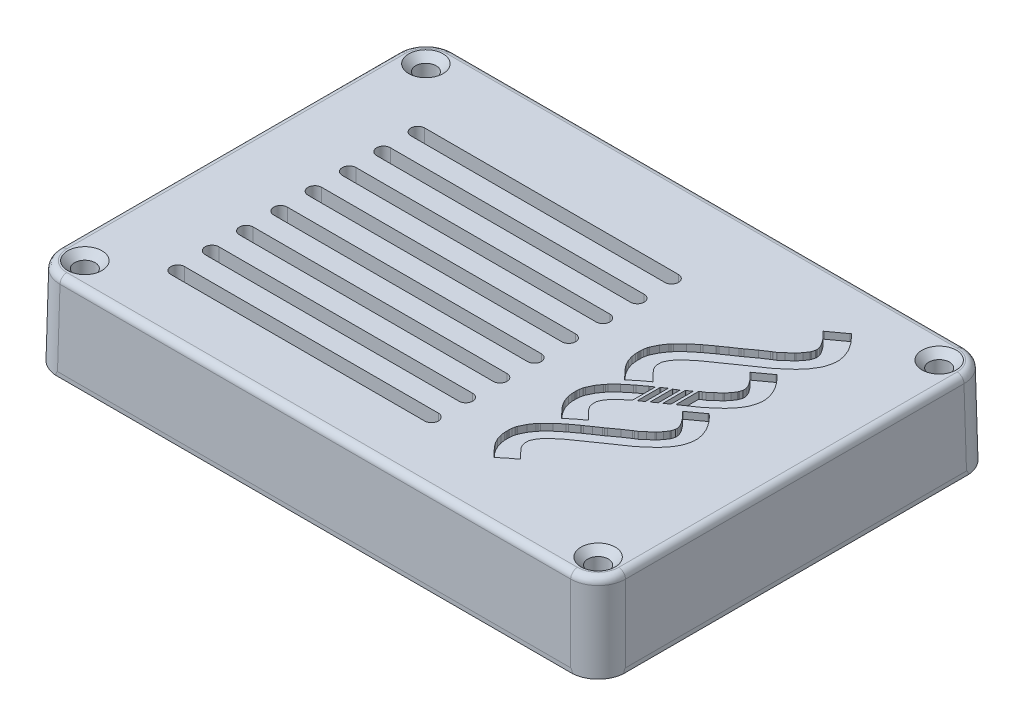
SolidWorks part; units mm, degrees
material "ABS PC"
ref_plane "Front Plane" through (0, 0, 0) normal (0, 0, 1) x (1, 0, 0)
ref_plane "Top Plane" through (0, 0, 0) normal (0, 1, 0) x (1, 0, 0)
ref_plane "Right Plane" through (0, 0, 0) normal (1, 0, 0) x (0, 0, -1)
sketch "Sketch1" plane through (0, 0, 0) normal (0, 1, 0) x (1, 0, 0)
  line L1 (-108.7297, 31.1354) -> (-25.9297, 31.1354)
  line L2 (-108.7297, 31.1354) -> (-108.7297, -26.5646)
  line L3 (-108.7297, -26.5646) -> (-25.9297, -26.5646)
  line L4 (-25.9297, 31.1354) -> (-25.9297, -26.5646)
  line L5 (-108.7297, 31.1354) -> (-25.9297, -26.5646) construction
  line L6 (-108.7297, -26.5646) -> (-25.9297, 31.1354) construction
  point P0 (-67.3297, 2.2854)
extrude "Boss-Extrude1" add sketch "Sketch1" along normal blind 12.6
chamfer "Chamfer1" distance 12 distance2 0.2 4 edges at (-25.9297, 12.6, -2.2854) (-67.3297, 12.6, -31.1354) (-108.7297, 12.6, -2.2854) (-67.3297, 12.6, 26.5646) first distance on face at (-25.9297, 6.3, -2.2854) first distance on face at (-67.3297, 6.3, -31.1354) first distance on face at (-108.7297, 6.3, -2.2854) first distance on face at (-67.3297, 6.3, 26.5646)
fillet "Fillet1" radius 4 4 edges at (-108.6297, 6.6, -31.0354) (-26.0297, 6.6, -31.0354) (-26.0297, 6.6, 26.4646) (-108.6297, 6.6, 26.4646)
sketch "Sketch2" plane through (0, 0, 0) normal (0, -1, 0) x (1, 0, 0)
  circle A0 centre (-104.7391, 22.5741) radius 1.5
  circle A1 centre (-29.9202, 22.5741) radius 1.5
  circle A2 centre (-104.7391, -27.1448) radius 1.5
  circle A3 centre (-29.9202, -27.1448) radius 1.5
extrude "Cut-Extrude1" cut sketch "Sketch2" against normal blind 12.6
fillet "Fillet2" radius 1 8 edges at (-107.3583, 12.6, -29.764) (-67.3297, 12.6, -30.9354) (-27.301, 12.6, -29.764) (-26.1297, 12.6, -2.2854) (-27.301, 12.6, 25.1933) (-67.3297, 12.6, 26.3646) (-107.3583, 12.6, 25.1933) (-108.5297, 12.6, -2.2854)
chamfer "Chamfer2" distance 1 angle 45 4 edges at (-104.7391, 12.6, 21.0741) (-29.9202, 12.6, 21.0741) (-29.9202, 12.6, -28.6448) (-104.7391, 12.6, -28.6448)
sketch "Sketch3" plane through (0, 0, 0) normal (0, -1, 0) x (1, 0, 0)
  line L0 (-105.0229, 26.5646) -> (-29.6364, 26.5646) construction
  line L1 (-99.7651, 22.0646) -> (-34.8942, 22.0646)
  line L2 (-104.2297, 17.6001) -> (-104.2297, -22.1708)
  line L3 (-99.7651, -26.6354) -> (-34.8942, -26.6354)
  line L4 (-30.4297, 17.6001) -> (-30.4297, -22.1708)
  line L5 (-100.7693, 23.0646) -> (-33.89, 23.0646)
  line L6 (-29.4297, 18.6043) -> (-29.4297, -23.175)
  line L7 (-108.7297, -27.4286) -> (-108.7297, 22.8579) construction
  line L8 (-25.9297, 22.8579) -> (-25.9297, -27.4286) construction
  line L9 (-29.6364, -31.1354) -> (-105.0229, -31.1354) construction
  line L10 (-100.7693, -27.6354) -> (-33.89, -27.6354)
  line L11 (-105.2297, 18.6043) -> (-105.2297, -23.175)
  arc A0 (-104.2297, 17.6001) -> (-99.7651, 22.0646) centre (-104.7391, 22.5741) ccw
  arc A1 (-34.8942, 22.0646) -> (-30.4297, 17.6001) centre (-29.9202, 22.5741) ccw
  arc A2 (-30.4297, -22.1708) -> (-34.8942, -26.6354) centre (-29.9202, -27.1448) ccw
  arc A3 (-99.7651, -26.6354) -> (-104.2297, -22.1708) centre (-104.7391, -27.1448) ccw
  arc A4 (-33.89, 23.0646) -> (-29.4297, 18.6043) centre (-29.9202, 22.5741) ccw
  arc A5 (-29.4297, -23.175) -> (-33.89, -27.6354) centre (-29.9202, -27.1448) ccw
  arc A6 (-100.7693, -27.6354) -> (-105.2297, -23.175) centre (-104.7391, -27.1448) ccw
  arc A7 (-105.2297, 18.6043) -> (-100.7693, 23.0646) centre (-104.7391, 22.5741) ccw
  point P0 (-67.3297, -2.2854)
  dimension "D5" = 1
  dimension "D1" = 4.5
  dimension "D2" = 4.5
  dimension "D3" = 4.5
  dimension "D4" = 4.5
extrude "Cut-Extrude2" cut sketch "Sketch3" against normal blind 10.4 contours A0 L1 A1 L4 A2 L3 A3 L2
extrude "Cut-Extrude-Thin1" cut sketch "Sketch3<4>" against normal blind 1 thin contours L11 A6 L10 A5 L6 A4 L5 A7 thin type one direction wall 1
sketch "Sketch3<4>" plane through (0, 0, 0) normal (0, -1, 0) x (1, 0, 0) same geometry as "Sketch3"
sketch "Sketch4" plane through (0, 12.6, 0) normal (0, 1, 0) x (1, 0, 0)
  line L0 (-96.7297, 18.9519) -> (-59.7297, 18.9519)
  line L1 (-96.7297, 16.9519) -> (-59.7297, 16.9519)
  line L2 (-30.1127, 29.9519) -> (-104.5466, 29.9519) construction
  line L3 (-96.7297, 18.9519) -> (-96.7297, 16.9519) construction
  line L4 (-59.7297, 18.9519) -> (-59.7297, 16.9519) construction
  line L5 (-96.7297, 13.9519) -> (-59.7297, 13.9519)
  line L6 (-96.7297, 11.9519) -> (-59.7297, 11.9519)
  line L7 (-96.7297, 13.9519) -> (-96.7297, 11.9519) construction
  line L8 (-59.7297, 13.9519) -> (-59.7297, 11.9519) construction
  line L9 (-96.7297, 8.9519) -> (-59.7297, 8.9519)
  line L10 (-96.7297, 6.9519) -> (-59.7297, 6.9519)
  line L11 (-96.7297, 8.9519) -> (-96.7297, 6.9519) construction
  line L12 (-59.7297, 8.9519) -> (-59.7297, 6.9519) construction
  line L13 (-96.7297, 3.9519) -> (-59.7297, 3.9519)
  line L14 (-96.7297, 1.9519) -> (-59.7297, 1.9519)
  line L15 (-96.7297, 3.9519) -> (-96.7297, 1.9519) construction
  line L16 (-59.7297, 3.9519) -> (-59.7297, 1.9519) construction
  line L17 (-96.7297, -1.0481) -> (-59.7297, -1.0481)
  line L18 (-96.7297, -3.0481) -> (-59.7297, -3.0481)
  line L19 (-96.7297, -1.0481) -> (-96.7297, -3.0481) construction
  line L20 (-59.7297, -1.0481) -> (-59.7297, -3.0481) construction
  line L21 (-96.7297, -6.0481) -> (-59.7297, -6.0481)
  line L22 (-96.7297, -8.0481) -> (-59.7297, -8.0481)
  line L23 (-96.7297, -6.0481) -> (-96.7297, -8.0481) construction
  line L24 (-59.7297, -6.0481) -> (-59.7297, -8.0481) construction
  line L25 (-96.7297, -11.0481) -> (-59.7297, -11.0481)
  line L26 (-96.7297, -13.0481) -> (-59.7297, -13.0481)
  line L27 (-96.7297, -11.0481) -> (-96.7297, -13.0481) construction
  line L28 (-59.7297, -11.0481) -> (-59.7297, -13.0481) construction
  line L29 (-96.7297, -16.0481) -> (-59.7297, -16.0481)
  line L30 (-96.7297, -18.0481) -> (-59.7297, -18.0481)
  line L31 (-96.7297, -16.0481) -> (-96.7297, -18.0481) construction
  line L32 (-59.7297, -16.0481) -> (-59.7297, -18.0481) construction
  line L33 (-108.7297, -22.5652) -> (-108.7297, 27.1359) construction
  arc A0 (-96.7297, 18.9519) -> (-96.7297, 16.9519) centre (-96.7297, 17.9519) ccw
  arc A1 (-59.7297, 16.9519) -> (-59.7297, 18.9519) centre (-59.7297, 17.9519) ccw
  arc A2 (-96.7297, 13.9519) -> (-96.7297, 11.9519) centre (-96.7297, 12.9519) ccw
  arc A3 (-59.7297, 11.9519) -> (-59.7297, 13.9519) centre (-59.7297, 12.9519) ccw
  arc A4 (-96.7297, 8.9519) -> (-96.7297, 6.9519) centre (-96.7297, 7.9519) ccw
  arc A5 (-59.7297, 6.9519) -> (-59.7297, 8.9519) centre (-59.7297, 7.9519) ccw
  arc A6 (-96.7297, 3.9519) -> (-96.7297, 1.9519) centre (-96.7297, 2.9519) ccw
  arc A7 (-59.7297, 1.9519) -> (-59.7297, 3.9519) centre (-59.7297, 2.9519) ccw
  arc A8 (-96.7297, -1.0481) -> (-96.7297, -3.0481) centre (-96.7297, -2.0481) ccw
  arc A9 (-59.7297, -3.0481) -> (-59.7297, -1.0481) centre (-59.7297, -2.0481) ccw
  arc A10 (-96.7297, -6.0481) -> (-96.7297, -8.0481) centre (-96.7297, -7.0481) ccw
  arc A11 (-59.7297, -8.0481) -> (-59.7297, -6.0481) centre (-59.7297, -7.0481) ccw
  arc A12 (-96.7297, -11.0481) -> (-96.7297, -13.0481) centre (-96.7297, -12.0481) ccw
  arc A13 (-59.7297, -13.0481) -> (-59.7297, -11.0481) centre (-59.7297, -12.0481) ccw
  arc A14 (-96.7297, -16.0481) -> (-96.7297, -18.0481) centre (-96.7297, -17.0481) ccw
  arc A15 (-59.7297, -18.0481) -> (-59.7297, -16.0481) centre (-59.7297, -17.0481) ccw
  dimension "D4" = 37
  dimension "D5" = 12
  dimension "D1" = 2
  dimension "D2" = 11
  dimension "D3" = 8
extrude "Cut-Extrude3" cut sketch "Sketch4" against normal blind 10.4
sketch "Sketch5" plane through (0, 12.6, -12.6) normal (0, -1, 0) x (1, 0, 0)
  line L156 (-52.4746, 25.5513) -> (-52.4746, 25.6597)
  line L157 (-52.4528, 25.2263) -> (-52.4746, 25.5513)
  line L158 (-52.372, 24.8216) -> (-52.4528, 25.2263)
  line L159 (-52.3429, 24.7362) -> (-52.372, 24.8216)
  line L160 (-52.2772, 24.543) -> (-52.3429, 24.7362)
  line L168 (-51.8523, 23.6409) -> (-52.2772, 24.543)
  line L169 (-51.3033, 22.8336) -> (-51.8523, 23.6409)
  line L170 (-51.1752, 22.6873) -> (-51.3033, 22.8336)
  line L171 (-51.01, 22.4982) -> (-51.1752, 22.6873)
  line L172 (-50.1017, 21.5946) -> (-51.01, 22.4982)
  line L173 (-49.0694, 20.7342) -> (-50.1017, 21.5946)
  line L174 (-48.8419, 20.5665) -> (-49.0694, 20.7342)
  line L175 (-47.8226, 19.8143) -> (-48.8419, 20.5665)
  line L176 (-47.7362, 19.7509) -> (-47.8226, 19.8143)
  line L177 (-47.7263, 19.7628) -> (-47.7362, 19.7509)
  line L178 (-47.5783, 19.6555) -> (-47.7263, 19.7628)
  line L179 (-46.7856, 19.0893) -> (-47.5783, 19.6555)
  line L180 (-45.9424, 18.5191) -> (-46.7856, 19.0893)
  line L181 (-45.7689, 18.4092) -> (-45.9424, 18.5191)
  line L182 (-45.5184, 18.218) -> (-45.7689, 18.4092)
  line L183 (-44.3725, 17.381) -> (-45.5184, 18.218)
  line L184 (-43.3778, 16.7096) -> (-44.3725, 17.381)
  line L185 (-43.2028, 16.6008) -> (-43.3778, 16.7096)
  line L186 (-43.1716, 16.5815) -> (-43.2028, 16.6008)
  line L187 (-42.8658, 16.3978) -> (-43.1716, 16.5815)
  line L188 (-42.8361, 16.3806) -> (-42.8658, 16.3978)
  line L189 (-42.2205, 15.8363) -> (-42.8361, 16.3806)
  line L190 (-41.5361, 15.2311) -> (-42.2205, 15.8363)
  line L191 (-41.4367, 15.1238) -> (-41.5361, 15.2311)
  line L192 (-40.9741, 14.591) -> (-41.4367, 15.1238)
  line L193 (-40.6043, 14.0279) -> (-40.9741, 14.591)
  line L194 (-40.5512, 13.9055) -> (-40.6043, 14.0279)
  line L195 (-40.5257, 13.8462) -> (-40.5512, 13.9055)
  line L196 (-40.3975, 13.406) -> (-40.5257, 13.8462)
  line L279 (-40.3975, 13.2394) -> (-40.3975, 13.406)
  line L280 (-40.3975, 13.141) -> (-40.3975, 13.2394)
  line L281 (-40.4564, 12.8456) -> (-40.3975, 13.141)
  line L282 (-40.596, 12.503) -> (-40.4564, 12.8456)
  line L283 (-40.6366, 12.43) -> (-40.596, 12.503)
  line L284 (-40.721, 12.2811) -> (-40.6366, 12.43)
  line L285 (-41.234, 11.5743) -> (-40.721, 12.2811)
  line L286 (-41.9054, 10.8758) -> (-41.234, 11.5743)
  line L287 (-42.0689, 10.7311) -> (-41.9054, 10.8758)
  line L288 (-42.1752, 10.6367) -> (-42.0689, 10.7311)
  line L289 (-42.0606, 10.5534) -> (-42.1752, 10.6367)
  line L290 (-39.9939, 9.0462) -> (-42.0606, 10.5534)
  line L291 (-39.9189, 8.9915) -> (-39.9939, 9.0462)
  line L292 (-39.8496, 9.0539) -> (-39.9189, 8.9915)
  line L293 (-39.7028, 9.1878) -> (-39.8496, 9.0539)
  line L294 (-39.2809, 9.6096) -> (-39.7028, 9.1878)
  line L295 (-38.8366, 10.1257) -> (-39.2809, 9.6096)
  line L296 (-38.4741, 10.6367) -> (-38.8366, 10.1257)
  line L297 (-38.2278, 11.0389) -> (-38.4741, 10.6367)
  line L298 (-38.1507, 11.1754) -> (-38.2278, 11.0389)
  line L299 (-38.0559, 11.3435) -> (-38.1507, 11.1754)
  line L300 (-37.7231, 12.1982) -> (-38.0559, 11.3435)
  line L301 (-37.5793, 12.9779) -> (-37.7231, 12.1982)
  line L302 (-37.5793, 13.2377) -> (-37.5793, 12.9779)
  line L303 (-37.5793, 13.4478) -> (-37.5793, 13.2377)
  line L304 (-37.671, 14.0763) -> (-37.5793, 13.4478)
  line L305 (-37.8835, 14.7774) -> (-37.671, 14.0763)
  line L306 (-37.9439, 14.917) -> (-37.8835, 14.7774)
  line L307 (-38.0148, 15.0795) -> (-37.9439, 14.917)
  line L308 (-38.2715, 15.5478) -> (-38.0148, 15.0795)
  line L309 (-38.6486, 16.0982) -> (-38.2715, 15.5478)
  line L310 (-39.0512, 16.5857) -> (-38.6486, 16.0982)
  line L311 (-39.3522, 16.9185) -> (-39.0512, 16.5857)
  line L312 (-39.4533, 17.0279) -> (-39.3522, 16.9185)
  line L313 (-39.458, 17.0326) -> (-39.4533, 17.0279)
  line L314 (-39.5564, 17.1295) -> (-39.458, 17.0326)
  line L315 (-39.5606, 17.1336) -> (-39.5564, 17.1295)
  line L316 (-39.9825, 17.5066) -> (-39.5606, 17.1336)
  line L317 (-41.1377, 18.5144) -> (-39.9825, 17.5066)
  line L318 (-41.1423, 18.5185) -> (-41.1377, 18.5144)
  line L319 (-41.1476, 18.5227) -> (-41.1423, 18.5185)
  line L320 (-41.9815, 19.0972) -> (-41.1476, 18.5227)
  line L321 (-42.0721, 19.1602) -> (-41.9815, 19.0972)
  line L322 (-44.0949, 20.555) -> (-42.0721, 19.1602)
  line L323 (-47.1137, 22.6722) -> (-44.0949, 20.555)
  line L324 (-47.3001, 22.8097) -> (-47.1137, 22.6722)
  line L529 (-48.1398, 23.5086) -> (-47.3001, 22.8097)
  line L530 (-48.8715, 24.2347) -> (-48.1398, 23.5086)
  line L531 (-49.0034, 24.3857) -> (-48.8715, 24.2347)
  line L532 (-49.0731, 24.4654) -> (-49.0034, 24.3857)
  line L533 (-49.3752, 24.9112) -> (-49.0731, 24.4654)
  line L534 (-49.6148, 25.419) -> (-49.3752, 24.9112)
  line L535 (-49.6528, 25.5289) -> (-49.6148, 25.419)
  line L536 (-49.6533, 25.5336) -> (-49.6528, 25.5289)
  line L537 (-49.6569, 25.6274) -> (-49.6533, 25.5336)
  line L538 (-49.6569, 25.6597) -> (-49.6569, 25.6274)
  line L539 (-49.6569, 25.6904) -> (-49.6569, 25.6597)
  line L540 (-49.6559, 25.7821) -> (-49.6569, 25.6904)
  line L541 (-49.6553, 25.792) -> (-49.6559, 25.7821)
  line L542 (-49.6553, 25.8034) -> (-49.6553, 25.792)
  line L543 (-49.6548, 25.8201) -> (-49.6553, 25.8034)
  line L544 (-49.6548, 25.8336) -> (-49.6548, 25.8201)
  line L545 (-49.6533, 25.9393) -> (-49.6548, 25.8336)
  line L546 (-49.6533, 25.9789) -> (-49.6533, 25.9393)
  line L547 (-49.6533, 25.993) -> (-49.6533, 25.9789)
  line L548 (-49.6539, 26.0336) -> (-49.6533, 25.993)
  line L549 (-49.6539, 26.0378) -> (-49.6539, 26.0336)
  line L550 (-49.6539, 26.0524) -> (-49.6539, 26.0378)
  line L551 (-49.6539, 26.1961) -> (-49.6539, 26.0524)
  line L552 (-49.5263, 26.6274) -> (-49.6539, 26.1961)
  line L553 (-49.31, 26.9946) -> (-49.5263, 26.6274)
  line L554 (-49.2654, 27.0492) -> (-49.31, 26.9946)
  line L555 (-49.2189, 27.1071) -> (-49.2654, 27.0492)
  line L556 (-49.072, 27.2753) -> (-49.2189, 27.1071)
  line L557 (-48.7933, 27.5774) -> (-49.072, 27.2753)
  line L558 (-48.4351, 27.9508) -> (-48.7933, 27.5774)
  line L559 (-48.109, 28.2815) -> (-48.4351, 27.9508)
  line L560 (-47.9996, 28.3909) -> (-48.109, 28.2815)
  line L561 (-47.9064, 28.4847) -> (-47.9996, 28.3909)
  line L562 (-48.0127, 28.5628) -> (-47.9064, 28.4847)
  line L563 (-48.7559, 29.1112) -> (-48.0127, 28.5628)
  line L564 (-48.869, 29.1946) -> (-48.7559, 29.1112)
  line L565 (-49.8991, 30.0352) -> (-48.869, 29.1946)
  line L566 (-49.9944, 30.1216) -> (-49.8991, 30.0352)
  line L567 (-50.0752, 30.1951) -> (-49.9944, 30.1216)
  line L568 (-50.1517, 30.1175) -> (-50.0752, 30.1951)
  line L569 (-50.2653, 30.0034) -> (-50.1517, 30.1175)
  line L570 (-50.6033, 29.6581) -> (-50.2653, 30.0034)
  line L571 (-50.981, 29.2612) -> (-50.6033, 29.6581)
  line L572 (-51.2829, 28.9295) -> (-50.981, 29.2612)
  line L573 (-51.4543, 28.731) -> (-51.2829, 28.9295)
  line L574 (-51.5085, 28.6628) -> (-51.4543, 28.731)
  line L575 (-51.599, 28.5503) -> (-51.5085, 28.6628)
  line L576 (-51.8444, 28.1893) -> (-51.599, 28.5503)
  line L577 (-52.1548, 27.5951) -> (-51.8444, 28.1893)
  line L578 (-52.383, 26.8878) -> (-52.1548, 27.5951)
  line L579 (-52.4715, 26.2795) -> (-52.383, 26.8878)
  line L580 (-52.4715, 26.0763) -> (-52.4715, 26.2795)
  line L581 (-52.4715, 26.0623) -> (-52.4715, 26.0763)
  line L582 (-52.4715, 26.0185) -> (-52.4715, 26.0623)
  line L583 (-52.4709, 26.0133) -> (-52.4715, 26.0185)
  line L584 (-52.4709, 25.9795) -> (-52.4709, 26.0133)
  line L585 (-52.4709, 25.9529) -> (-52.4709, 25.9795)
  line L586 (-52.472, 25.8727) -> (-52.4709, 25.9529)
  line L587 (-52.472, 25.8628) -> (-52.472, 25.8727)
  line L588 (-52.4725, 25.8435) -> (-52.472, 25.8628)
  line L589 (-52.4731, 25.8289) -> (-52.4725, 25.8435)
  line L590 (-52.4746, 25.706) -> (-52.4731, 25.8289)
  line L591 (-52.4746, 25.6597) -> (-52.4746, 25.706)
  line L592 (-39.9189, -0.8716) -> (-39.9939, -0.8169)
  line L593 (-39.8502, -0.8091) -> (-39.9189, -0.8716)
  line L594 (-39.7033, -0.6752) -> (-39.8502, -0.8091)
  line L595 (-39.2809, -0.2533) -> (-39.7033, -0.6752)
  line L596 (-38.8366, 0.2629) -> (-39.2809, -0.2533)
  line L597 (-38.4741, 0.7738) -> (-38.8366, 0.2629)
  line L598 (-38.2278, 1.1757) -> (-38.4741, 0.7738)
  line L599 (-38.1507, 1.3122) -> (-38.2278, 1.1757)
  line L600 (-38.0559, 1.4805) -> (-38.1507, 1.3122)
  line L601 (-37.7231, 2.3352) -> (-38.0559, 1.4805)
  line L602 (-37.5793, 3.1153) -> (-37.7231, 2.3352)
  line L603 (-37.5793, 3.3754) -> (-37.5793, 3.1153)
  line L604 (-37.5793, 3.5852) -> (-37.5793, 3.3754)
  line L605 (-37.671, 4.2134) -> (-37.5793, 3.5852)
  line L606 (-37.8835, 4.9144) -> (-37.671, 4.2134)
  line L607 (-37.9439, 5.0538) -> (-37.8835, 4.9144)
  line L608 (-38.0148, 5.2165) -> (-37.9439, 5.0538)
  line L609 (-38.2715, 5.6847) -> (-38.0148, 5.2165)
  line L610 (-38.6486, 6.2352) -> (-38.2715, 5.6847)
  line L611 (-39.0512, 6.7227) -> (-38.6486, 6.2352)
  line L612 (-39.3517, 7.0555) -> (-39.0512, 6.7227)
  line L613 (-39.4528, 7.1648) -> (-39.3517, 7.0555)
  line L614 (-39.4559, 7.1675) -> (-39.4528, 7.1648)
  line L615 (-39.458, 7.1696) -> (-39.4559, 7.1675)
  line L616 (-39.5559, 7.2664) -> (-39.458, 7.1696)
  line L617 (-39.5585, 7.2686) -> (-39.5559, 7.2664)
  line L618 (-39.5606, 7.2706) -> (-39.5585, 7.2686)
  line L619 (-39.9825, 7.6435) -> (-39.5606, 7.2706)
  line L620 (-41.1377, 8.6513) -> (-39.9825, 7.6435)
  line L621 (-41.1423, 8.656) -> (-41.1377, 8.6513)
  line L622 (-41.1476, 8.6596) -> (-41.1423, 8.656)
  line L623 (-41.9815, 9.2346) -> (-41.1476, 8.6596)
  line L624 (-42.0721, 9.2972) -> (-41.9815, 9.2346)
  line L625 (-43.495, 10.2779) -> (-42.0721, 9.2972)
  line L626 (-43.495, 6.9237) -> (-43.495, 10.2779)
  line L627 (-43.4699, 6.9076) -> (-43.495, 6.9237)
  line L628 (-43.2268, 6.7525) -> (-43.4699, 6.9076)
  line L629 (-43.2028, 6.7378) -> (-43.2268, 6.7525)
  line L630 (-43.171, 6.7186) -> (-43.2028, 6.7378)
  line L631 (-42.8652, 6.5346) -> (-43.171, 6.7186)
  line L632 (-42.8361, 6.5175) -> (-42.8652, 6.5346)
  line L633 (-42.2205, 5.9732) -> (-42.8361, 6.5175)
  line L634 (-41.5361, 5.3685) -> (-42.2205, 5.9732)
  line L635 (-41.4367, 5.2612) -> (-41.5361, 5.3685)
  line L636 (-40.9741, 4.7279) -> (-41.4367, 5.2612)
  line L637 (-40.6039, 4.1648) -> (-40.9741, 4.7279)
  line L638 (-40.5507, 4.0424) -> (-40.6039, 4.1648)
  line L639 (-40.5251, 3.9831) -> (-40.5507, 4.0424)
  line L640 (-40.3975, 3.543) -> (-40.5251, 3.9831)
  line L641 (-40.3975, 3.3762) -> (-40.3975, 3.543)
  line L642 (-40.3975, 3.2779) -> (-40.3975, 3.3762)
  line L643 (-40.4559, 2.9825) -> (-40.3975, 3.2779)
  line L644 (-40.596, 2.6399) -> (-40.4559, 2.9825)
  line L645 (-40.6366, 2.567) -> (-40.596, 2.6399)
  line L646 (-40.721, 2.4181) -> (-40.6366, 2.567)
  line L647 (-41.234, 1.7112) -> (-40.721, 2.4181)
  line L648 (-41.9054, 1.0128) -> (-41.234, 1.7112)
  line L649 (-42.0689, 0.868) -> (-41.9054, 1.0128)
  line L650 (-42.1752, 0.7738) -> (-42.0689, 0.868)
  line L651 (-42.0606, 0.6904) -> (-42.1752, 0.7738)
  line L652 (-39.9939, -0.8169) -> (-42.0606, 0.6904)
  line L653 (-47.3866, 13.0148) -> (-47.2116, 12.8836)
  line L654 (-48.1815, 13.6841) -> (-47.3866, 13.0148)
  line L655 (-48.8777, 14.379) -> (-48.1815, 13.6841)
  line L656 (-49.0034, 14.5227) -> (-48.8777, 14.379)
  line L657 (-49.0731, 14.6024) -> (-49.0034, 14.5227)
  line L658 (-49.3752, 15.0481) -> (-49.0731, 14.6024)
  line L659 (-49.6148, 15.556) -> (-49.3752, 15.0481)
  line L660 (-49.6528, 15.6659) -> (-49.6148, 15.556)
  line L661 (-49.6533, 15.6706) -> (-49.6528, 15.6659)
  line L662 (-49.6569, 15.7645) -> (-49.6533, 15.6706)
  line L663 (-49.6569, 15.7967) -> (-49.6569, 15.7645)
  line L664 (-49.6569, 15.8273) -> (-49.6569, 15.7967)
  line L665 (-49.6559, 15.9191) -> (-49.6569, 15.8273)
  line L666 (-49.6553, 15.9289) -> (-49.6559, 15.9191)
  line L667 (-49.6553, 15.9576) -> (-49.6553, 15.9289)
  line L668 (-49.6553, 15.9711) -> (-49.6553, 15.9576)
  line L669 (-49.6533, 16.0763) -> (-49.6553, 15.9711)
  line L670 (-49.6533, 16.1159) -> (-49.6533, 16.0763)
  line L671 (-49.6533, 16.13) -> (-49.6533, 16.1159)
  line L672 (-49.6539, 16.1705) -> (-49.6533, 16.13)
  line L673 (-49.6539, 16.1749) -> (-49.6539, 16.1705)
  line L674 (-49.6539, 16.1894) -> (-49.6539, 16.1749)
  line L675 (-49.6539, 16.3331) -> (-49.6539, 16.1894)
  line L676 (-49.5263, 16.7644) -> (-49.6539, 16.3331)
  line L677 (-49.31, 17.1315) -> (-49.5263, 16.7644)
  line L678 (-49.2657, 17.1862) -> (-49.31, 17.1315)
  line L679 (-49.2195, 17.2446) -> (-49.2657, 17.1862)
  line L680 (-49.072, 17.4123) -> (-49.2195, 17.2446)
  line L681 (-48.7939, 17.7143) -> (-49.072, 17.4123)
  line L682 (-48.4351, 18.0878) -> (-48.7939, 17.7143)
  line L683 (-48.109, 18.4185) -> (-48.4351, 18.0878)
  line L684 (-47.9996, 18.5279) -> (-48.109, 18.4185)
  line L685 (-47.9064, 18.6216) -> (-47.9996, 18.5279)
  line L686 (-48.0127, 18.7003) -> (-47.9064, 18.6216)
  line L687 (-48.7559, 19.2482) -> (-48.0127, 18.7003)
  line L688 (-48.869, 19.3315) -> (-48.7559, 19.2482)
  line L689 (-49.8991, 20.1722) -> (-48.869, 19.3315)
  line L690 (-49.9944, 20.2586) -> (-49.8991, 20.1722)
  line L691 (-50.0746, 20.332) -> (-49.9944, 20.2586)
  line L692 (-50.1517, 20.2545) -> (-50.0746, 20.332)
  line L693 (-50.2653, 20.1404) -> (-50.1517, 20.2545)
  line L694 (-50.6033, 19.7951) -> (-50.2653, 20.1404)
  line L695 (-50.981, 19.3982) -> (-50.6033, 19.7951)
  line L696 (-51.2829, 19.0665) -> (-50.981, 19.3982)
  line L697 (-51.4543, 18.868) -> (-51.2829, 19.0665)
  line L698 (-51.5085, 18.7998) -> (-51.4543, 18.868)
  line L699 (-51.599, 18.6873) -> (-51.5085, 18.7998)
  line L700 (-51.8444, 18.3263) -> (-51.599, 18.6873)
  line L701 (-52.1548, 17.7321) -> (-51.8444, 18.3263)
  line L702 (-52.383, 17.0247) -> (-52.1548, 17.7321)
  line L703 (-52.4715, 16.4164) -> (-52.383, 17.0247)
  line L704 (-52.4715, 16.2134) -> (-52.4715, 16.4164)
  line L705 (-52.4715, 16.1992) -> (-52.4715, 16.2134)
  line L706 (-52.4715, 16.156) -> (-52.4715, 16.1992)
  line L707 (-52.4709, 16.1509) -> (-52.4715, 16.156)
  line L708 (-52.4709, 16.117) -> (-52.4709, 16.1509)
  line L709 (-52.4709, 16.0904) -> (-52.4709, 16.117)
  line L710 (-52.472, 16.0096) -> (-52.4709, 16.0904)
  line L711 (-52.472, 15.9998) -> (-52.472, 16.0096)
  line L712 (-52.4725, 15.9806) -> (-52.472, 15.9998)
  line L713 (-52.4731, 15.9659) -> (-52.4725, 15.9806)
  line L714 (-52.4746, 15.843) -> (-52.4731, 15.9659)
  line L715 (-52.4746, 15.7967) -> (-52.4746, 15.843)
  line L716 (-52.4746, 15.6882) -> (-52.4746, 15.7967)
  line L717 (-52.4528, 15.3634) -> (-52.4746, 15.6882)
  line L718 (-52.3725, 14.9586) -> (-52.4528, 15.3634)
  line L719 (-52.3433, 14.8732) -> (-52.3725, 14.9586)
  line L720 (-52.2777, 14.68) -> (-52.3433, 14.8732)
  line L721 (-51.8523, 13.7779) -> (-52.2777, 14.68)
  line L722 (-51.3028, 12.9706) -> (-51.8523, 13.7779)
  line L723 (-51.1747, 12.8243) -> (-51.3028, 12.9706)
  line L724 (-51.0096, 12.6352) -> (-51.1747, 12.8243)
  line L725 (-50.1017, 11.732) -> (-51.0096, 12.6352)
  line L726 (-49.0694, 10.8711) -> (-50.1017, 11.732)
  line L727 (-48.8419, 10.7033) -> (-49.0694, 10.8711)
  line L728 (-47.8226, 9.9519) -> (-48.8419, 10.7033)
  line L729 (-47.7362, 9.8877) -> (-47.8226, 9.9519)
  line L730 (-47.7263, 9.8997) -> (-47.7362, 9.8877)
  line L731 (-47.6851, 9.8701) -> (-47.7263, 9.8997)
  line L732 (-47.2559, 9.5607) -> (-47.6851, 9.8701)
  line L733 (-47.2116, 9.529) -> (-47.2559, 9.5607)
  line L734 (-47.2116, 12.8836) -> (-47.2116, 9.529)
  line L735 (-44.5376, 7.7462) -> (-44.5981, 7.7883)
  line L736 (-43.958, 7.3555) -> (-44.5376, 7.7462)
  line L737 (-43.9028, 7.3191) -> (-43.958, 7.3555)
  line L738 (-43.9028, 10.5748) -> (-43.9028, 7.3191)
  line L739 (-44.0949, 10.7033) -> (-43.9028, 10.5748)
  line L740 (-44.5981, 11.0445) -> (-44.0949, 10.7033)
  line L741 (-44.5981, 7.9248) -> (-44.5981, 11.0445)
  line L742 (-44.5981, 7.7883) -> (-44.5981, 7.9248)
  line L743 (-46.8043, 12.592) -> (-46.1085, 12.1045)
  line L744 (-46.8043, 9.2399) -> (-46.8043, 12.592)
  line L745 (-46.7481, 9.2003) -> (-46.8043, 9.2399)
  line L746 (-46.1679, 8.8071) -> (-46.7481, 9.2003)
  line L747 (-46.1085, 8.768) -> (-46.1679, 8.8071)
  line L748 (-46.1085, 12.1045) -> (-46.1085, 8.768)
  line L749 (-45.6376, 8.52) -> (-45.7012, 8.5639)
  line L750 (-45.3528, 8.3363) -> (-45.6376, 8.52)
  line L751 (-45.0695, 8.1582) -> (-45.3528, 8.3363)
  line L752 (-45.0058, 8.1169) -> (-45.0695, 8.1582)
  line L753 (-45.0058, 11.3305) -> (-45.0058, 8.1169)
  line L754 (-45.7012, 11.8186) -> (-45.0058, 11.3305)
  line L755 (-45.7012, 8.5639) -> (-45.7012, 11.8186)
  line L756 (-52.8752, 5.9743) -> (-52.8752, 6.0888)
  line L757 (-52.8523, 5.6305) -> (-52.8752, 5.9743)
  line L758 (-52.7673, 5.2029) -> (-52.8523, 5.6305)
  line L759 (-52.7367, 5.1128) -> (-52.7673, 5.2029)
  line L760 (-52.6673, 4.9091) -> (-52.7367, 5.1128)
  line L761 (-52.2189, 3.9582) -> (-52.6673, 4.9091)
  line L762 (-51.6397, 3.1071) -> (-52.2189, 3.9582)
  line L763 (-51.5048, 2.953) -> (-51.6397, 3.1071)
  line L764 (-51.3309, 2.7539) -> (-51.5048, 2.953)
  line L765 (-50.3746, 1.8024) -> (-51.3309, 2.7539)
  line L766 (-49.2876, 0.8962) -> (-50.3746, 1.8024)
  line L767 (-49.0481, 0.7196) -> (-49.2876, 0.8962)
  line L768 (-47.9757, -0.071) -> (-49.0481, 0.7196)
  line L769 (-47.8747, -0.1456) -> (-47.9757, -0.071)
  line L770 (-47.8642, -0.133) -> (-47.8747, -0.1456)
  line L771 (-47.7091, -0.2456) -> (-47.8642, -0.133)
  line L772 (-46.8788, -0.8383) -> (-47.7091, -0.2456)
  line L773 (-45.9966, -1.4352) -> (-46.8788, -0.8383)
  line L774 (-45.8148, -1.5497) -> (-45.9966, -1.4352)
  line L775 (-45.5512, -1.7507) -> (-45.8148, -1.5497)
  line L776 (-44.346, -2.6314) -> (-45.5512, -1.7507)
  line L777 (-43.2991, -3.3383) -> (-44.346, -2.6314)
  line L778 (-43.1147, -3.4528) -> (-43.2991, -3.3383)
  line L779 (-43.0819, -3.4732) -> (-43.1147, -3.4528)
  line L780 (-42.7606, -3.6664) -> (-43.0819, -3.4732)
  line L781 (-42.7299, -3.6841) -> (-42.7606, -3.6664)
  line L782 (-42.0835, -4.256) -> (-42.7299, -3.6841)
  line L783 (-41.3637, -4.8913) -> (-42.0835, -4.256)
  line L784 (-41.2595, -5.0044) -> (-41.3637, -4.8913)
  line L785 (-40.7736, -5.5642) -> (-41.2595, -5.0044)
  line L786 (-40.3861, -6.1544) -> (-40.7736, -5.5642)
  line L787 (-40.3303, -6.2825) -> (-40.3861, -6.1544)
  line L788 (-40.3039, -6.3445) -> (-40.3303, -6.2825)
  line L789 (-40.1699, -6.8039) -> (-40.3039, -6.3445)
  line L790 (-40.1699, -6.9778) -> (-40.1699, -6.8039)
  line L791 (-40.1699, -7.0804) -> (-40.1699, -6.9778)
  line L792 (-40.2314, -7.3888) -> (-40.1699, -7.0804)
  line L793 (-40.3778, -7.7461) -> (-40.2314, -7.3888)
  line L794 (-40.4199, -7.8221) -> (-40.3778, -7.7461)
  line L795 (-40.5085, -7.9784) -> (-40.4199, -7.8221)
  line L796 (-41.0471, -8.721) -> (-40.5085, -7.9784)
  line L797 (-41.7522, -9.4544) -> (-41.0471, -8.721)
  line L798 (-41.9241, -9.6065) -> (-41.7522, -9.4544)
  line L799 (-42.0481, -9.7163) -> (-41.9241, -9.6065)
  line L800 (-41.9143, -9.8143) -> (-42.0481, -9.7163)
  line L801 (-39.7397, -11.3997) -> (-41.9143, -9.8143)
  line L802 (-39.6522, -11.4637) -> (-39.7397, -11.3997)
  line L803 (-39.5715, -11.3909) -> (-39.6522, -11.4637)
  line L804 (-39.345, -11.1847) -> (-39.5715, -11.3909)
  line L805 (-38.5038, -10.2611) -> (-39.345, -11.1847)
  line L806 (-37.8934, -9.3534) -> (-38.5038, -10.2611)
  line L807 (-37.7814, -9.1554) -> (-37.8934, -9.3534)
  line L808 (-37.6814, -8.9778) -> (-37.7814, -9.1554)
  line L809 (-37.3299, -8.0763) -> (-37.6814, -8.9778)
  line L810 (-37.1783, -7.2528) -> (-37.3299, -8.0763)
  line L811 (-37.1783, -6.9789) -> (-37.1783, -7.2528)
  line L812 (-37.1783, -6.7576) -> (-37.1783, -6.9789)
  line L813 (-37.2752, -6.0945) -> (-37.1783, -6.7576)
  line L814 (-37.4996, -5.355) -> (-37.2752, -6.0945)
  line L815 (-37.5632, -5.2076) -> (-37.4996, -5.355)
  line L816 (-37.6663, -4.9694) -> (-37.5632, -5.2076)
  line L817 (-38.3059, -3.9628) -> (-37.6663, -4.9694)
  line L818 (-39.0153, -3.132) -> (-38.3059, -3.9628)
  line L819 (-39.1533, -2.9831) -> (-39.0153, -3.132)
  line L820 (-39.1585, -2.9778) -> (-39.1533, -2.9831)
  line L821 (-39.2621, -2.8758) -> (-39.1585, -2.9778)
  line L822 (-39.2673, -2.8705) -> (-39.2621, -2.8758)
  line L823 (-39.7111, -2.4789) -> (-39.2673, -2.8705)
  line L824 (-40.9262, -1.418) -> (-39.7111, -2.4789)
  line L825 (-40.932, -1.4128) -> (-40.9262, -1.418)
  line L826 (-40.9382, -1.4085) -> (-40.932, -1.4128)
  line L827 (-41.8153, -0.8039) -> (-40.9382, -1.4085)
  line L828 (-41.9111, -0.7377) -> (-41.8153, -0.8039)
  line L829 (-44.0392, 0.7295) -> (-41.9111, -0.7377)
  line L830 (-47.2143, 2.9565) -> (-44.0392, 0.7295)
  line L831 (-47.41, 3.1008) -> (-47.2143, 2.9565)
  line L832 (-48.293, 3.8358) -> (-47.41, 3.1008)
  line L833 (-49.0616, 4.5992) -> (-48.293, 3.8358)
  line L834 (-49.2002, 4.7576) -> (-49.0616, 4.5992)
  line L835 (-49.273, 4.8409) -> (-49.2002, 4.7576)
  line L836 (-49.5892, 5.3077) -> (-49.273, 4.8409)
  line L837 (-49.8403, 5.8393) -> (-49.5892, 5.3077)
  line L838 (-49.8804, 5.9544) -> (-49.8403, 5.8393)
  line L839 (-49.8809, 5.9591) -> (-49.8804, 5.9544)
  line L840 (-49.8846, 6.0555) -> (-49.8809, 5.9591)
  line L841 (-49.8846, 6.0888) -> (-49.8846, 6.0555)
  line L842 (-49.8846, 6.1211) -> (-49.8846, 6.0888)
  line L843 (-49.8835, 6.2175) -> (-49.8846, 6.1211)
  line L844 (-49.8829, 6.2279) -> (-49.8835, 6.2175)
  line L845 (-49.8829, 6.2399) -> (-49.8829, 6.2279)
  line L846 (-49.8824, 6.2571) -> (-49.8829, 6.2399)
  line L847 (-49.8824, 6.2711) -> (-49.8824, 6.2571)
  line L848 (-49.8804, 6.3831) -> (-49.8824, 6.2711)
  line L849 (-49.8804, 6.4248) -> (-49.8804, 6.3831)
  line L850 (-49.8804, 6.4367) -> (-49.8804, 6.4248)
  line L851 (-49.8809, 6.4717) -> (-49.8804, 6.4367)
  line L852 (-49.8809, 6.4866) -> (-49.8809, 6.4717)
  line L853 (-49.8809, 6.5019) -> (-49.8809, 6.4866)
  line L854 (-49.8809, 6.5815) -> (-49.8809, 6.5019)
  line L855 (-49.8439, 6.8191) -> (-49.8809, 6.5815)
  line L856 (-49.7481, 7.1019) -> (-49.8439, 6.8191)
  line L857 (-49.6173, 7.3451) -> (-49.7481, 7.1019)
  line L858 (-49.5137, 7.4951) -> (-49.6173, 7.3451)
  line L859 (-49.4757, 7.5421) -> (-49.5137, 7.4951)
  line L860 (-49.4272, 7.6029) -> (-49.4757, 7.5421)
  line L861 (-49.2726, 7.7795) -> (-49.4272, 7.6029)
  line L862 (-48.9799, 8.0972) -> (-49.2726, 7.7795)
  line L863 (-48.6023, 8.4899) -> (-48.9799, 8.0972)
  line L864 (-48.26, 8.8378) -> (-48.6023, 8.4899)
  line L865 (-48.1449, 8.953) -> (-48.26, 8.8378)
  line L866 (-48.0356, 9.0623) -> (-48.1449, 8.953)
  line L867 (-48.16, 9.1539) -> (-48.0356, 9.0623)
  line L868 (-48.9418, 9.7306) -> (-48.16, 9.1539)
  line L869 (-49.0605, 9.818) -> (-48.9418, 9.7306)
  line L870 (-50.1434, 10.7019) -> (-49.0605, 9.818)
  line L871 (-50.2439, 10.7929) -> (-50.1434, 10.7019)
  line L872 (-50.3382, 10.8784) -> (-50.2439, 10.7929)
  line L873 (-50.4277, 10.7883) -> (-50.3382, 10.8784)
  line L874 (-50.5476, 10.668) -> (-50.4277, 10.7883)
  line L875 (-50.9033, 10.3045) -> (-50.5476, 10.668)
  line L876 (-51.3007, 9.8867) -> (-50.9033, 10.3045)
  line L877 (-51.6184, 9.5367) -> (-51.3007, 9.8867)
  line L878 (-51.7987, 9.3284) -> (-51.6184, 9.5367)
  line L879 (-51.8559, 9.2565) -> (-51.7987, 9.3284)
  line L880 (-51.9517, 9.1378) -> (-51.8559, 9.2565)
  line L881 (-52.2105, 8.7576) -> (-51.9517, 9.1378)
  line L882 (-52.5381, 8.1301) -> (-52.2105, 8.7576)
  line L883 (-52.7788, 7.3837) -> (-52.5381, 8.1301)
  line L884 (-52.872, 6.7415) -> (-52.7788, 7.3837)
  line L885 (-52.872, 6.5273) -> (-52.872, 6.7415)
  line L886 (-52.872, 6.5123) -> (-52.872, 6.5273)
  line L887 (-52.872, 6.4664) -> (-52.872, 6.5123)
  line L888 (-52.8715, 6.4607) -> (-52.872, 6.4664)
  line L889 (-52.8715, 6.4254) -> (-52.8715, 6.4607)
  line L890 (-52.8715, 6.3977) -> (-52.8715, 6.4254)
  line L891 (-52.873, 6.3134) -> (-52.8715, 6.3977)
  line L892 (-52.873, 6.303) -> (-52.873, 6.3134)
  line L893 (-52.8736, 6.2836) -> (-52.873, 6.303)
  line L894 (-52.8741, 6.2685) -> (-52.8736, 6.2836)
  line L895 (-52.8752, 6.1378) -> (-52.8741, 6.2685)
  line L896 (-52.8752, 6.0888) -> (-52.8752, 6.1378)
extrude "Cut-Extrude5" cut sketch "Sketch5" along normal blind 1
